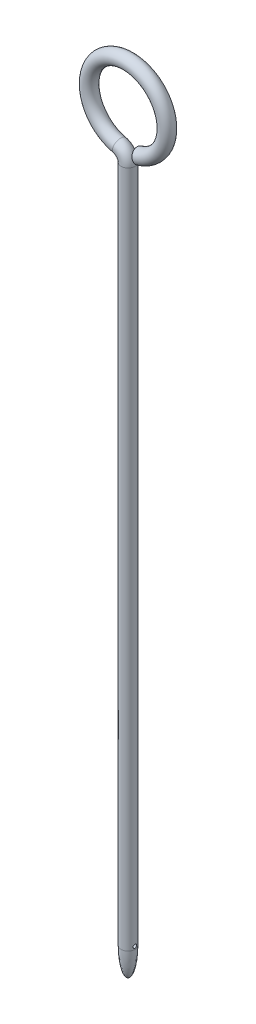
SolidWorks part; units mm, degrees
material "Brass"
ref_plane "Front Plane" through (0, 0, 0) normal (0, 0, 1) x (1, 0, 0)
ref_plane "Top Plane" through (0, 0, 0) normal (0, 1, 0) x (1, 0, 0)
ref_plane "Right Plane" through (0, 0, 0) normal (1, 0, 0) x (0, 0, -1)
sketch "Sketch1" plane through (0, 0, 0) normal (0, 1, 0) x (1, 0, 0)
  circle A0 centre (0, 0) radius 1.5875
  dimension "D1" = 3.175
extrude "Boss-Extrude1" add sketch "Sketch1" along normal blind 152.4
sketch "Sketch2" plane through (0, 0, 0) normal (0, 0, 1) x (1, 0, 0)
  line L0 (0, 152.4) -> (0, 154.94)
  line L1 (1.5875, 152.4) -> (-1.5875, 152.4) construction
  arc A0 (-1.9756, 157.4165) -> (2.54, 157.5648) centre (0, 166.0842) cw
  arc A1 (0, 154.94) -> (-1.9756, 157.4165) centre (-2.54, 154.94) ccw
  dimension "D1" = 2.54
  dimension "D2" = 8.89
  dimension "D3" = 2.54
  dimension "D4" = 2.54
sketch "Sketch3" plane through (0, 152.4, 0) normal (0, 1, 0) x (1, 0, 0)
  circle A0 centre (0, 0) radius 1.5875
sweep "Sweep1" add profiles "Sketch3" path "Sketch2"
dome "Dome1" faces to dome 1 distance 6.35 reverse direction no elliptical dome yes face at (0, 0, 1.5875) parameters "D1"=6.35
sketch "Sketch5" plane through (0, 0, 0) normal (1, 0, 0) x (0, 0, -1)
  circle A0 centre (0, 0.635) radius 0.3969
  dimension "D1" = 0.7937
  dimension "D2" = 0.635
extrude "Cut-Extrude1" cut sketch "Sketch5" against normal through all and the other way through all
